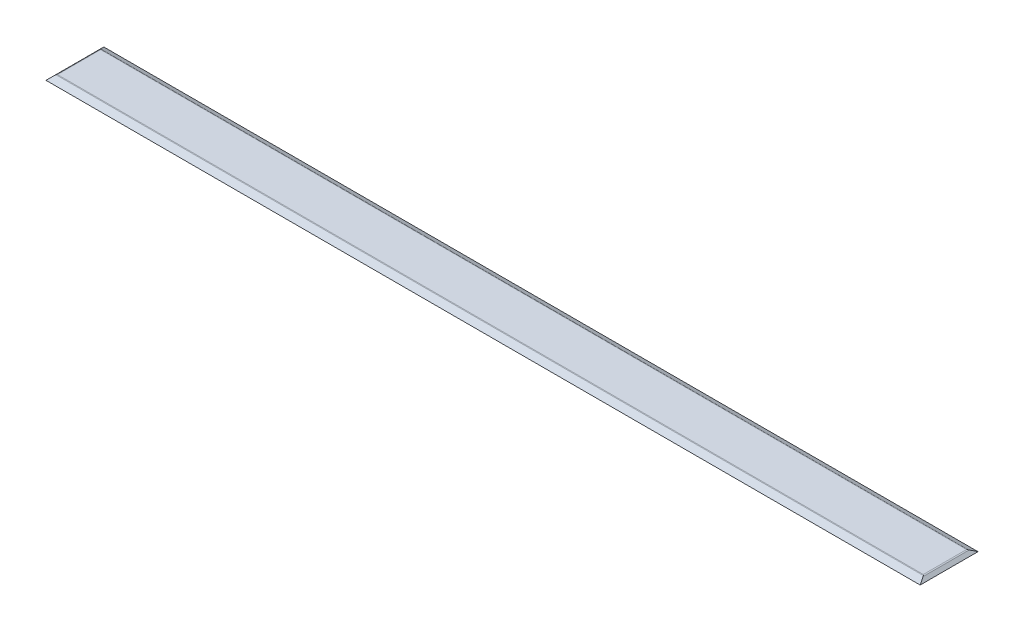
SolidWorks part; units mm, degrees
ref_plane "Front Plane" through (0, 0, 0) normal (0, 0, 1) x (1, 0, 0)
ref_plane "Top Plane" through (0, 0, 0) normal (0, 1, 0) x (1, 0, 0)
ref_plane "Right Plane" through (0, 0, 0) normal (1, 0, 0) x (0, 0, -1)
sketch "Sketch1" plane through (0, 0, 0) normal (1, 0, 0) x (0, 0, -1)
  line L0 (-84, -10) -> (-64, 0)
  line L1 (-64, 0) -> (64, 0)
  line L2 (64, 0) -> (84, -10)
  line L3 (-84, -10) -> (84, -10)
  line L4 (0, 0) -> (0, -10) construction
  dimension "D1" = 128
  dimension "D2" = 20
  dimension "D3" = 10
extrude "Boss-Extrude1" add sketch "Sketch1" along normal mid plane 2540
chamfer "Chamfer1" distance 10 angle 45 2 edges at (1270, 0, 0) (-1270, 0, 0)
fillet "Fillet1" radius 5 4 edges at (1260, 0, 0) (0, 0, 64) (-1260, 0, 0) (0, 0, -64)
shell "Shell2" thickness 1 removed face at (0, -10, 0)
